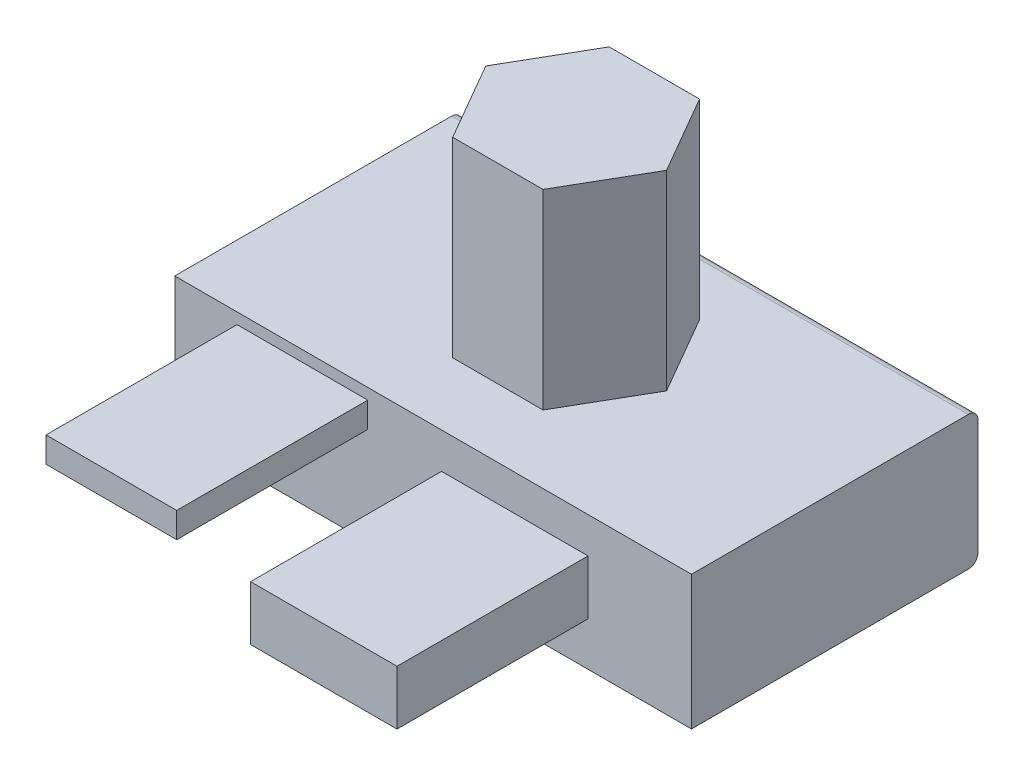
SolidWorks part; units mm, degrees
ref_plane "Front Plane" through (0, 0, 0) normal (0, 0, 1) x (1, 0, 0)
ref_plane "Top Plane" through (0, 0, 0) normal (0, 1, 0) x (1, 0, 0)
ref_plane "Right Plane" through (0, 0, 0) normal (1, 0, 0) x (0, 0, -1)
sketch "Sketch1" plane through (0, 0, 0) normal (0, 0, 1) x (1, 0, 0)
  line L1 (-68.7035, -17.821) -> (68.7035, -17.821)
  line L2 (-68.7035, -17.821) -> (-68.7035, 17.821)
  line L3 (-68.7035, 17.821) -> (68.7035, 17.821)
  line L4 (68.7035, -17.821) -> (68.7035, 17.821)
  line L5 (-68.7035, -17.821) -> (68.7035, 17.821) construction
  line L6 (-68.7035, 17.821) -> (68.7035, -17.821) construction
  point P0 (0, 0)
extrude "Boss-Extrude1" add sketch "Sketch1" along normal blind 76.2 contours L1 L4 L3 L2
sketch "Sketch2" plane through (0, 17.821, 0) normal (0, 1, 0) x (1, 0, 0)
  line L1 (23.159, -37.2907) -> (11.1437, -16.4796)
  line L2 (11.1437, -16.4796) -> (-12.8869, -16.4796)
  line L3 (-12.8869, -16.4796) -> (-24.9022, -37.2907)
  line L4 (-24.9022, -37.2907) -> (-12.8869, -58.1018)
  line L5 (-12.8869, -58.1018) -> (11.1437, -58.1018)
  line L6 (11.1437, -58.1018) -> (23.159, -37.2907)
  circle A0 centre (-0.8716, -37.2907) radius 20.8111 construction
extrude "Boss-Extrude2" add sketch "Sketch2" along normal blind 50.8
sketch "Sketch3" plane through (0, -17.821, 0) normal (0, -1, 0) x (1, 0, 0)
  circle A0 centre (0, 36.7926) radius 26.0998
sketch "Sketch4" plane through (0, 0, 76.2) normal (0, 0, 1) x (1, 0, 0)
  line L1 (-52.1439, 14.8868) -> (-17.3813, 14.8868)
  line L2 (-52.1439, 14.8868) -> (-52.1439, 8.1274)
  line L3 (-52.1439, 8.1274) -> (-17.3813, 8.1274)
  line L4 (-17.3813, 14.8868) -> (-17.3813, 8.1274)
  line L5 (-52.1439, 14.8868) -> (-17.3813, 8.1274) construction
  line L6 (-52.1439, 8.1274) -> (-17.3813, 14.8868) construction
  line L7 (2.2531, 8.2883) -> (41.2001, 8.2883)
  line L8 (2.2531, 8.2883) -> (2.2531, -6.1961)
  line L9 (2.2531, -6.1961) -> (41.2001, -6.1961)
  line L10 (41.2001, 8.2883) -> (41.2001, -6.1961)
  line L11 (2.2531, 8.2883) -> (41.2001, -6.1961) construction
  line L12 (2.2531, -6.1961) -> (41.2001, 8.2883) construction
  point P0 (-34.7626, 11.5071)
  point P5 (21.7266, 1.0461)
extrude "Boss-Extrude4" add sketch "Sketch4" along normal blind 50.8
fillet "Fillet2" radius 2.54 2 edges at (0, -17.821, 0) (0, 17.821, 0)
